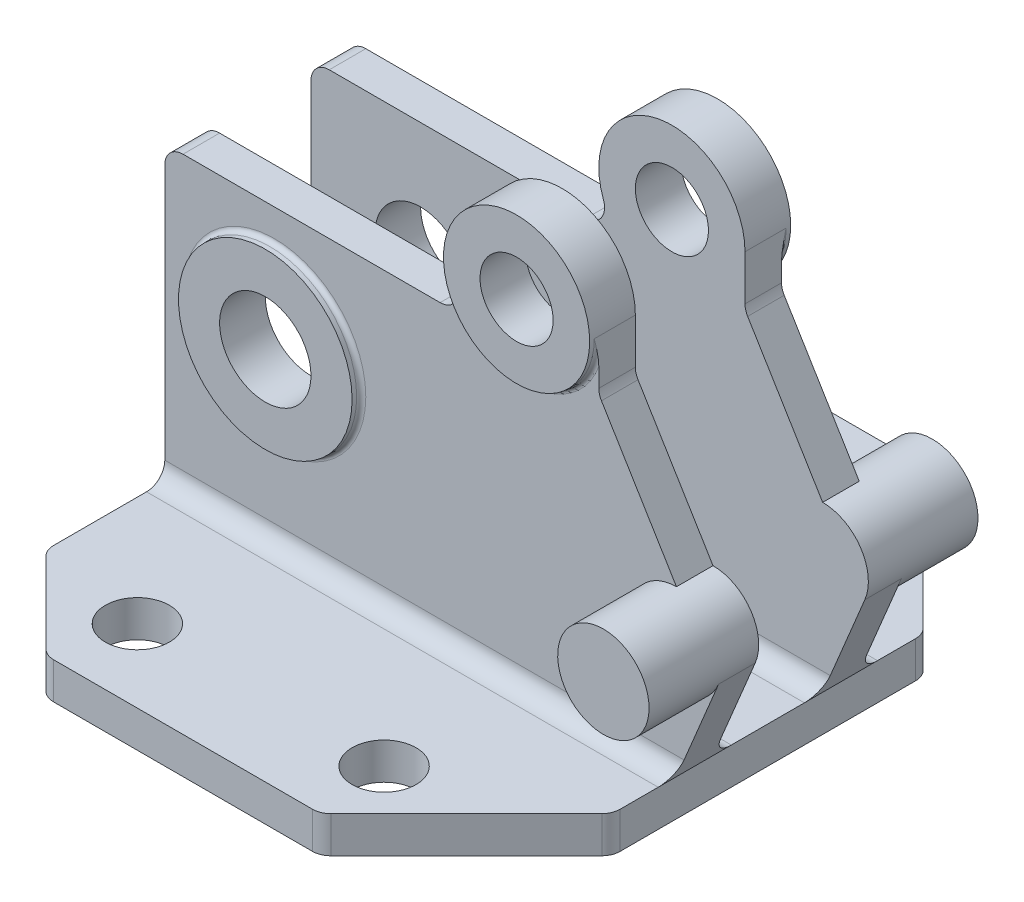
SolidWorks part; units mm, degrees
material "Cast Carbon Steel"
ref_plane "Front Plane" through (0, 0, 0) normal (0, 0, 1) x (1, 0, 0)
ref_plane "Top Plane" through (0, 0, 0) normal (0, 1, 0) x (1, 0, 0)
ref_plane "Right Plane" through (0, 0, 0) normal (1, 0, 0) x (0, 0, -1)
sketch "Sketch1" plane through (0, 0, 0) normal (0, 1, 0) x (1, 0, 0)
  line L0 (0, 33) -> (56, 33) construction
  line L1 (0, 0) -> (56, 0)
  line L2 (0, 0) -> (0, 66)
  line L3 (0, 66) -> (56, 66)
  line L4 (56, 0) -> (56, 66)
  circle A0 centre (12, 8) radius 3.5
  circle A1 centre (39, 8) radius 3.5
  circle A2 centre (39, 58) radius 3.5
  circle A3 centre (12, 58) radius 3.5
  dimension "D5" = 7
  dimension "D1" = 66
  dimension "D2" = 56
  dimension "D3" = 27
  dimension "D4" = 8
  dimension "D6" = 12
extrude "Boss-Extrude1" add sketch "Sketch1" along normal blind 4
chamfer "Chamfer1" distance 16 angle 45 2 edges at (56, 2, -66) (56, 2, 0)
chamfer "Chamfer2" distance 10 angle 45 2 edges at (0, 2, -66) (0, 2, 0)
fillet "Fillet1" radius 2 8 edges at (0, 2, -10) (10, 2, 0) (40, 2, 0) (56, 2, -16) (40, 2, -66) (10, 2, -66) (0, 2, -56) (56, 2, -50)
ref_plane "Plane1" through (0, 0, -33) normal (0, 0, 1) x (1, 0, 0)
sketch "Sketch2" plane through (0, 0, -33) normal (0, 0, 1) x (1, 0, 0)
  line L0 (0, 4) -> (56, 4)
  line L1 (0, 4) -> (0, 36)
  line L2 (0, 36) -> (33.6905, 36)
  line L8 (56, 4) -> (60.6154, 15.0769)
  line L9 (47.5, 41.5) -> (47.5, 36)
  line L10 (47.5, 36) -> (56, 22)
  arc A1 (60.6154, 15.0769) -> (56, 22) centre (56, 17) ccw
  arc A2 (47.5, 41.5) -> (33.6905, 36) centre (39.5, 41.5) ccw
  circle A3 centre (39.5, 41.5) radius 8
  circle A4 centre (56, 17) radius 5
  circle A5 centre (12, 23) radius 9.5
  circle A6 centre (39.5, 41.5) radius 4
  circle A7 centre (12, 23) radius 5
  dimension "D4" = 10
  dimension "D5" = 37.5
  dimension "D7" = 8
  dimension "D10" = 19
  dimension "D11" = 8
  dimension "D12" = 10
  dimension "D1" = 32
  dimension "D2" = 39.5
  dimension "D3" = 13
  dimension "D6" = 16.5
  dimension "D8" = 12
  dimension "D9" = 19
extrude "Boss-Extrude2" add sketch "Sketch2" along normal mid plane 20 contours A4 L10 L9 A3 L2 L1 L0 L8 A5 region at (29.6413, 18.7228, -33)
extrude "Boss-Extrude3" add sketch "Sketch2<3>" along normal mid plane 22 contours A5 A7 | A2 A3 A6 region at (36.6236, 48.722, -33) region at (2.7687, 23, -33)
sketch "Sketch2<3>" plane through (0, 0, -33) normal (0, 0, 1) x (1, 0, 0) same geometry as "Sketch2"
extrude "Boss-Extrude4" add sketch "Sketch2<4>" along normal mid plane 36 contours A1 A4 region at (56, 17, -33)
sketch "Sketch2<4>" plane through (0, 0, -33) normal (0, 0, 1) x (1, 0, 0) same geometry as "Sketch2"
sketch "Sketch4" plane through (0, 0, 0) normal (-1, 0, 0) x (0, 0, 1)
  line L0 (-43, 4) -> (-23, 4) construction
  line L1 (-22, 49.5) -> (-44, 49.5) construction
  line L2 (-39, 49.5) -> (-27, 49.5)
  line L3 (-39, 49.5) -> (-39, 4)
  line L4 (-39, 4) -> (-27, 4)
  line L5 (-27, 49.5) -> (-27, 4)
  point P10 (-33, 4)
  point P11 (-33, 4)
  dimension "D1" = 12
extrude "Cut-Extrude1" cut sketch "Sketch4" against normal through all
fillet "Fillet2" radius 2 1 edges at (33.6905, 36, -41)
fillet "Fillet3" radius 2 2 edges at (47.5, 36, -25) (47.5, 36, -41)
fillet "Fillet4" radius 2 4 edges at (28, 4, -27) (28, 4, -43) (28, 4, -39) (28, 4, -23)
fillet "Fillet5" radius 2 2 edges at (0, 36, -25) (0, 36, -41)
fillet "Fillet6" radius 0.5 4 edges at (40.9227, 33.6275, -23) (40.9227, 33.6275, -43) (21.5, 23, -43) (21.5, 23, -23)
equation "\"A\"= 66"
equation "\"B\"= 56"
